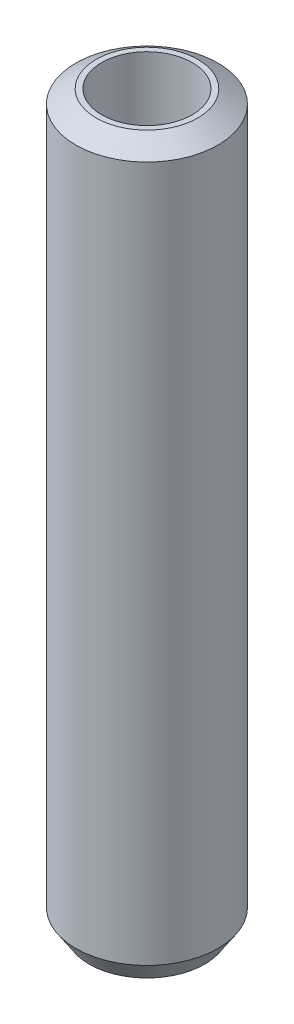
SolidWorks part; units mm, degrees
ref_plane "Front Plane" through (0, 0, 0) normal (0, 0, 1) x (1, 0, 0)
ref_plane "Top Plane" through (0, 0, 0) normal (0, 1, 0) x (1, 0, 0)
ref_plane "Right Plane" through (0, 0, 0) normal (1, 0, 0) x (0, 0, -1)
sketch "Sketch1" plane through (0, 0, 0) normal (0, 1, 0) x (1, 0, 0)
  circle A0 centre (0, 0) radius 25
  dimension "SHAFT_OD" = 50
extrude "Boss-Extrude1" add sketch "Sketch1" along normal blind 256.4615
sketch "Sketch2" plane through (0, 0, 0) normal (0, 1, 0) x (1, 0, 0)
  circle A0 centre (0, 0) radius 15.9299
  dimension "BORE_D" = 31.8599
extrude "Cut-Extrude1" cut sketch "Sketch2" along normal through all
chamfer "Chamfer1" distance 4.6843 angle 56.716 2 edges at (0, 256.4615, 25) (0, 0, 25) first distance on face at (0, 256.4615, 25) first distance on face at (0, 0, 15.9299)
